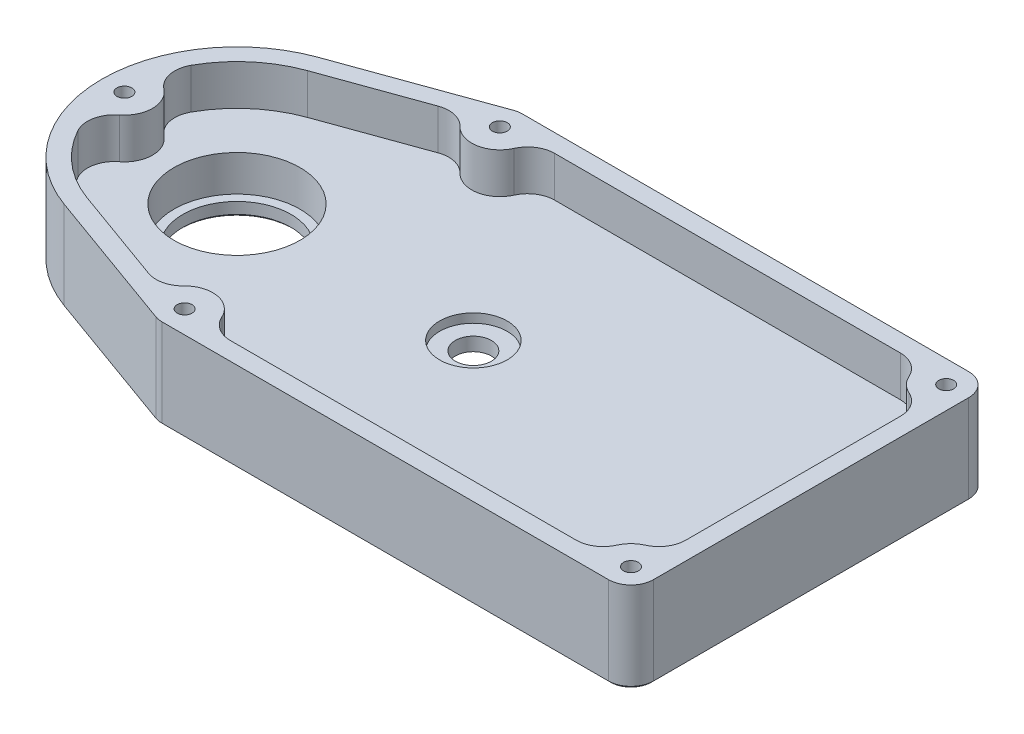
SolidWorks part; units mm, degrees
material "Alumina"
ref_plane "Plan de face" through (0, 0, 0) normal (0, 0, 1) x (1, 0, 0)
ref_plane "Plan de dessus" through (0, 0, 0) normal (0, 1, 0) x (1, 0, 0)
ref_plane "Plan de droite" through (0, 0, 0) normal (1, 0, 0) x (0, 0, -1)
sketch "Sketch2" plane through (0, 0, 0) normal (0, 1, 0) x (1, 0, 0)
  line L0 (-30, 40) -> (75, 40)
  line L1 (75, 40) -> (75, -40)
  line L2 (-30, 40) -> (-62.6732, 28.2224)
  line L3 (-62.6732, -28.2224) -> (-30, -40)
  line L4 (19.6, -22.6) -> (-19.6, -22.6)
  line L5 (22.6, -19.6) -> (22.6, 19.6)
  line L6 (19.6, 22.6) -> (-19.6, 22.6)
  line L7 (-22.6, -19.6) -> (-22.6, 19.6)
  line L8 (22.6, -22.6) -> (-22.6, 22.6) construction
  line L9 (22.6, 22.6) -> (-22.6, -22.6) construction
  line L10 (-30, -40) -> (75, -40)
  circle A0 centre (0, 0) radius 4
  circle A1 centre (-52.5, 0) radius 12
  arc A3 (-62.6732, 28.2224) -> (-62.6732, -28.2224) centre (-52.5, 0) ccw
  arc A5 (-19.6, 22.6) -> (-22.6, 19.6) centre (-19.6, 19.6) ccw
  arc A6 (-19.6, -22.6) -> (-22.6, -19.6) centre (-19.6, -19.6) cw
  arc A7 (19.6, -22.6) -> (22.6, -19.6) centre (19.6, -19.6) ccw
  arc A8 (22.6, 19.6) -> (19.6, 22.6) centre (19.6, 19.6) ccw
  dimension "D4" = 24
  dimension "D5" = 3
  dimension "D6" = 30
  dimension "D9" = 105
  dimension "D1" = 127.5
  dimension "D2" = 45.2
  dimension "D3" = 45.2
  dimension "D7" = 80
  dimension "D8" = 30
extrude "Boss-Extrude1" add sketch "Sketch2" along normal blind 20 contours L0 L2 A3 L3 L10 L1 A8 L5 A7 L4 A6 L7 A5 L6 A1 | L5 A8 L6 A5 L7 A6 L4 A7 A0 region at (22.5, 0, -38.2335) region at (0, 0, 21.9608)
fillet "Fillet1" radius 5 4 edges at (-30, 10, 40) (75, 10, 40) (75, 10, -40) (-30, 10, -40)
extrude "Cut-Extrude1" cut sketch "Sketch2<3>" along normal blind 6 contours L5 A8 L6 A5 L7 A6 L4 A7 A0 region at (0, 0, 21.9608)
sketch "Sketch2<3>" plane through (0, 0, 0) normal (0, 1, 0) x (1, 0, 0) same geometry as "Sketch2"
sketch "Sketch3" plane through (0, 20, 0) normal (0, 1, 0) x (1, 0, 0)
  circle A0 centre (-52.5, 0) radius 14
  dimension "D1" = 28
extrude "Cut-Extrude2" cut sketch "Sketch3" along direction (0, 1, 0) on the side against the normal offset from surface (17 mm away) 3 up to face at (0, 0, 0)
sketch "Sketch4" plane through (0, 20, 0) normal (0, 1, 0) x (1, 0, 0)
  circle A0 centre (0, 0) radius 7.5
  dimension "D1" = 15
extrude "Cut-Extrude3" cut sketch "Sketch4" against normal offset from surface (11 mm away) 3 up to face at (0, 6, 4)
hole_wizard "Tap Drill for M4 Tap1" positions "Sketch5" profile "Sketch6" hole size "M4" standard "ISO"
sketch "Sketch5" plane through (0, 20, 0) normal (0, 1, 0) x (1, 0, 0)
  line L0 (-90, 0) -> (75, 0) construction
  line L1 (75, 35) -> (75, -35) construction
  line L2 (0, 40) -> (0, -40) construction
  line L3 (-29.1263, 40) -> (70, 40) construction
  line L4 (-29.1263, -40) -> (70, -40) construction
  arc A0 (-62.6732, 28.2224) -> (-62.6732, -28.2224) centre (-52.5, 0) ccw construction
  arc A9 (75, 35) -> (70, 40) centre (70, 35) ccw construction
  arc A10 (70, -40) -> (75, -35) centre (70, -35) ccw construction
  arc A11 (-30.8219, -39.7037) -> (-29.1263, -40) centre (-29.1263, -35) ccw construction
  arc A12 (-29.1263, 40) -> (-30.8219, 39.7037) centre (-29.1263, 35) ccw construction
  point P10 (-77.5, 0)
  point P12 (-29.1263, 35)
  point P14 (-29.1263, -35)
  point P16 (70, -35)
  point P18 (70, 35)
  dimension "D1" = 25
sketch "Sketch6" plane through (70, 20, -35) normal (1, 0, 0) x (0, 0, 1)
  line L0 (0, 0) -> (0, 13.9914)
  line L1 (0, 13.9914) -> (1.65, 13)
  line L2 (1.65, 13) -> (1.65, 0)
  line L5 (1.65, 0) -> (0, 0)
  line L10 (0, 13.9914) -> (-1.65, 13) construction
  line L11 (0, -6.35) -> (0, 107.95) construction
  dimension "Hole Dia." = 3.3
  dimension "Hole Depth" = 13
  dimension "Drill Angle" = 118
sketch "Sketch7" plane through (0, 20, 0) normal (0, 1, 0) x (1, 0, 0)
  line L0 (75, 35) -> (75, -35) construction
  line L10 (-61.3168, -24.4594) -> (-29.4655, -35.9407)
  line L11 (-29.1263, -36) -> (70, -36)
  line L12 (71, -35) -> (71, 35)
  line L13 (70, 36) -> (-29.1263, 36)
  line L14 (-29.4655, 35.9407) -> (-61.3168, 24.4594)
  line L15 (-61.3168, -24.4594) -> (-35.2694, -33.8486)
  line L16 (-22.9569, -36) -> (63.8305, -36)
  line L17 (71, -28.8305) -> (71, 28.8305)
  line L18 (63.8305, 36) -> (-22.9569, 36)
  line L19 (-35.2694, 33.8486) -> (-61.3168, 24.4594)
  circle A0 centre (-29.1263, 35) radius 1.65 construction
  circle A1 centre (-29.1263, -35) radius 1.65 construction
  circle A2 centre (-77.5, 0) radius 1.65 construction
  circle A3 centre (70, 35) radius 1.65 construction
  circle A4 centre (70, -35) radius 1.65 construction
  arc A8 (-77.7387, -6.2454) -> (-77.7387, 6.2454) centre (-77.5, 0) ccw
  arc A10 (-29.4655, -35.9407) -> (-29.1263, -36) centre (-29.1263, -35) ccw
  arc A11 (70, -36) -> (71, -35) centre (70, -35) ccw
  arc A12 (71, 35) -> (70, 36) centre (70, 35) ccw
  arc A13 (-29.1263, 36) -> (-29.4655, 35.9407) centre (-29.1263, 35) ccw
  arc A14 (-61.3168, 24.4594) -> (-61.3168, -24.4594) centre (-52.5, 0) ccw
  arc A19 (-61.3168, 24.4594) -> (-77.7387, 6.2454) centre (-52.5, 0) ccw
  arc A21 (-35.2694, 33.8486) -> (-22.9569, 36) centre (-29.1263, 35) ccw
  arc A24 (63.8305, 36) -> (71, 28.8305) centre (70, 35) ccw
  arc A27 (-22.9569, -36) -> (-35.2694, -33.8486) centre (-29.1263, -35) ccw
  arc A28 (-77.7387, -6.2454) -> (-61.3168, -24.4594) centre (-52.5, 0) ccw
  arc A30 (71, -28.8305) -> (63.8305, -36) centre (70, -35) ccw
  dimension "D2" = 6.25
  dimension "D3" = 4
  dimension "D1" = 4
extrude "Cut-Extrude4" cut sketch "Sketch7" against normal blind 9
fillet "Fillet2" radius 6 10 edges at (71, 15.5, -28.8305) (63.8305, 15.5, -36) (71, 15.5, 28.8305) (63.8305, 15.5, 36) (-35.2694, 15.5, 33.8486) (-22.9569, 15.5, 36) (-22.9569, 15.5, -36) (-35.2694, 15.5, -33.8486) (-77.7387, 15.5, -6.2454) (-77.7387, 15.5, 6.2454)
chamfer "Chamfer1" distance 0.5 angle 45 19 edges at (-52.5, 0, 12) (-22.6, 0, 0) (-21.7213, 0, 21.7213) (-21.7213, 0, -21.7213) (0, 0, 22.6) (0, 0, -22.6) (21.7213, 0, 21.7213) (21.7213, 0, -21.7213) (22.6, 0, 0) (75, 0, 0) (73.5355, 0, -38.5355) (73.5355, 0, 38.5355) (20.4368, 0, -40) (20.4368, 0, 40) (-29.987, 0, -39.9254) (-29.987, 0, 39.9254) (-46.7475, 0, -33.9631) (-46.7475, 0, 33.9631) (-82.5, 0, 0)
